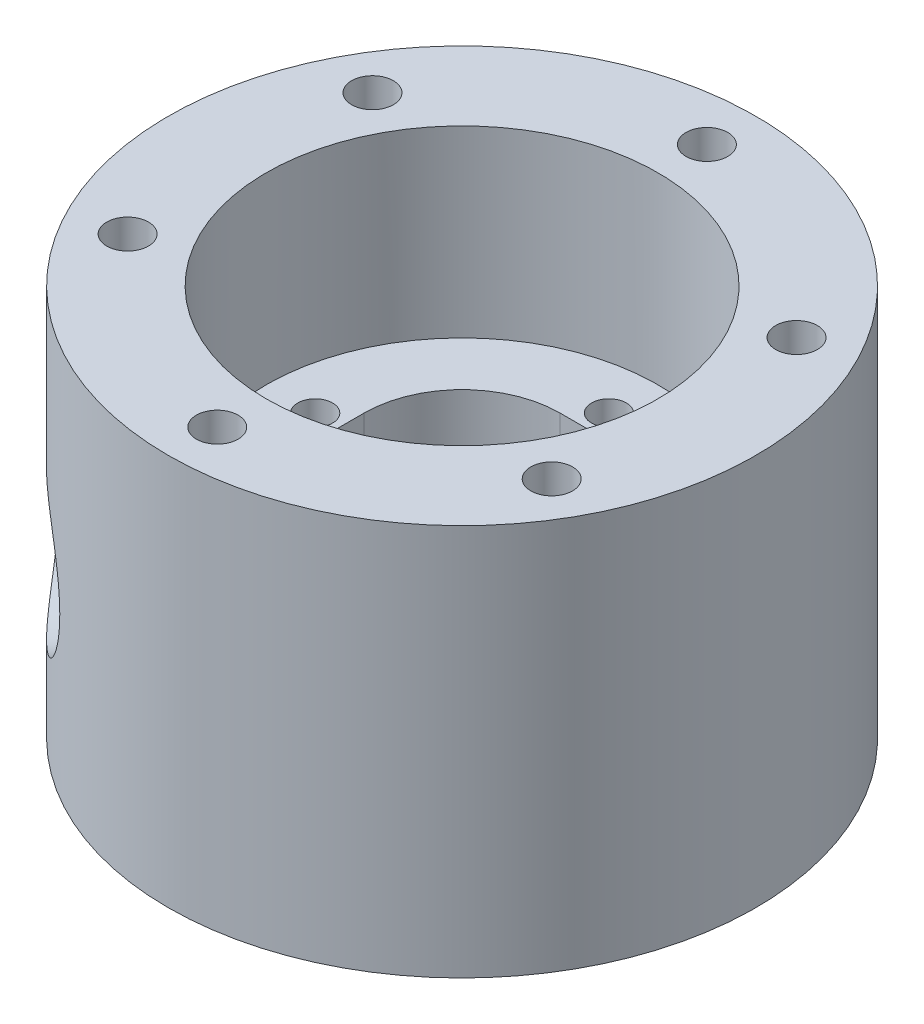
SolidWorks part; units mm, degrees
material "6061 Alloy"
ref_plane "Front Plane" through (0, 0, 0) normal (0, 0, 1) x (1, 0, 0)
ref_plane "Top Plane" through (0, 0, 0) normal (0, 1, 0) x (1, 0, 0)
ref_plane "Right Plane" through (0, 0, 0) normal (1, 0, 0) x (0, 0, -1)
sketch "Sketch1" plane through (0, 0, 0) normal (0, 1, 0) x (1, 0, 0)
  circle A1 centre (0, 0) radius 19.05
  dimension "D2" = 38.1
extrude "Boss-Extrude1" add sketch "Sketch1" along normal blind 25.4
sketch "Sketch3" plane through (0, 0, 0) normal (0, -1, 0) x (1, 0, 0)
  circle A0 centre (0, 0) radius 11.1125
  dimension "D1" = 22.225
extrude "Cut-Extrude1" cut sketch "Sketch3" against normal blind 7.1437
sketch "Sketch4" plane through (0, 25.4, 0) normal (0, 1, 0) x (1, 0, 0)
  line L1 (-1.5875, 7.9375) -> (1.5875, 7.9375)
  line L2 (-7.9375, 1.5875) -> (-7.9375, -1.5875)
  line L3 (-1.5875, -7.9375) -> (1.5875, -7.9375)
  line L4 (7.9375, 1.5875) -> (7.9375, -1.5875)
  arc A0 (1.5875, -7.9375) -> (7.9375, -1.5875) centre (1.5875, -1.5875) ccw
  arc A1 (1.5875, 7.9375) -> (7.9375, 1.5875) centre (1.5875, 1.5875) cw
  arc A2 (-7.9375, -1.5875) -> (-1.5875, -7.9375) centre (-1.5875, -1.5875) ccw
  arc A3 (-1.5875, 7.9375) -> (-7.9375, 1.5875) centre (-1.5875, 1.5875) ccw
  point P6 (7.9375, -7.9375)
  point P9 (7.9375, 7.9375)
  point P14 (-7.9375, 7.9375)
  dimension "D3" = 6.35
  dimension "D1" = 15.875
  dimension "D2" = 15.875
  dimension "D4" = 7.9375
  dimension "D5" = 7.9375
extrude "Cut-Extrude2" cut sketch "Sketch4" against normal blind 18.2562
sketch "Sketch5" plane through (0, 25.4, 0) normal (0, 1, 0) x (1, 0, 0)
  circle A0 centre (0, 0) radius 12.7
  dimension "D1" = 25.4
extrude "Cut-Extrude3" cut sketch "Sketch5" against normal blind 11.9062
hole_wizard "#4-40 Tapped Hole1" positions "Sketch7" profile "Sketch6" tap size "#4-40" standard "Ansi Inch" end condition through all
sketch "Sketch7" plane through (0, 13.4937, 0) normal (0, 1, 0) x (-1, 0, 0)
  point P0 (0, -9.525)
  dimension "D1" = 9.525
sketch "Sketch6" plane through (0, 13.4937, -9.525) normal (1, 0, 0) x (0, 0, 1)
  line L0 (0, 0) -> (0, 13.4937)
  line L1 (0, 13.4937) -> (1.1303, 13.4937)
  line L2 (1.1303, 13.4937) -> (1.1303, 0)
  line L5 (1.1303, 0) -> (0, 0)
  line L11 (0, -6.35) -> (0, 107.95) construction
  dimension "Thread Major Dia." = 2.2606
  dimension "Thru Tap Drill Depth" = 13.4937
pattern_circular "CirPattern1" count 4 over 360 about axis through (0, 25.4, 0) along (0, 1, 0) of "#4-40 Tapped Hole1"
ref_axis "Axis1" through (0, 13.4937, 0) along (0, 1, 0)
ref_plane "Plane1" through (0, 0, 0) normal (0.7071, 0, -0.7071) x (-0.7071, 0, -0.7071)
sketch "Sketch8" plane through (0, 0, 0) normal (0.7071, 0, -0.7071) x (-0.7071, 0, -0.7071)
  line L0 (0, 13.4937) -> (0, 25.4) construction
  line L1 (-19.05, 0) -> (19.05, 0) construction
  circle A0 centre (0, 10.3187) radius 4.7625
  dimension "D1" = 9.525
  dimension "D2" = 10.3187
extrude "Cut-Extrude6" cut sketch "Sketch8" against normal through all
hole_wizard "#6-32 Tapped Hole1" positions "Sketch10" profile "Sketch9" tap size "#6-32" standard "Ansi Inch"
sketch "Sketch10" plane through (0, 25.4, 0) normal (0, 1, 0) x (-1, 0, 0)
  point P0 (0, -15.875)
  dimension "D1" = 15.875
sketch "Sketch9" plane through (0, 25.4, -15.875) normal (1, 0, 0) x (0, 0, 1)
  line L0 (0, 0) -> (0, 11.9887)
  line L1 (0, 11.9887) -> (1.3525, 11.176)
  line L2 (1.3525, 11.176) -> (1.3525, 0)
  line L5 (1.3525, 0) -> (0, 0)
  line L10 (0, 11.9887) -> (-1.3526, 11.176) construction
  line L11 (0, -6.35) -> (0, 107.95) construction
  dimension "Tap Drill Dia." = 2.7051
  dimension "Tap Drill Depth" = 11.176
  dimension "Drill Angle" = 118
pattern_circular "CirPattern2" count 6 over 360 about axis through (0, 13.4937, 0) along (0, 1, 0) of "#6-32 Tapped Hole1"
